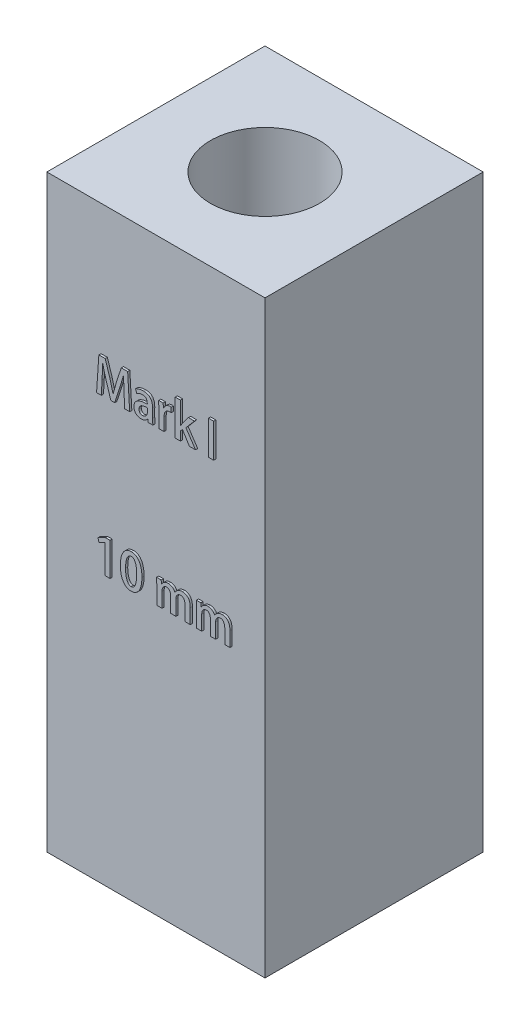
SolidWorks part; units mm, degrees
ref_plane "Alzado" through (0, 0, 0) normal (0, 0, 1) x (1, 0, 0)
ref_plane "Planta" through (0, 0, 0) normal (0, 1, 0) x (1, 0, 0)
ref_plane "Vista lateral" through (0, 0, 0) normal (1, 0, 0) x (0, 0, -1)
sketch "Croquis1" plane through (0, 0, 0) normal (0, 1, 0) x (1, 0, 0)
  line L1 (-5, 5) -> (5, 5)
  line L2 (-5, 5) -> (-5, -5)
  line L3 (-5, -5) -> (5, -5)
  line L4 (5, 5) -> (5, -5)
  line L5 (-5, 5) -> (5, -5) construction
  line L6 (-5, -5) -> (5, 5) construction
  circle A0 centre (0, 0) radius 2.5
  point P0 (0, 0)
  dimension "D1" = 5
  dimension "D2" = 10
extrude "Saliente-Extruir1" add sketch "Croquis1" along normal blind 27
sketch "Croquis2" plane through (0, 0, 5) normal (0, 0, 1) x (1, 0, 0)
  text T0 "Mark I\r\n \r\n10 mm" font "@Adobe Heiti Std R" height in points 5
split line "Línea de partición1"
extrude "Saliente-Extruir2" add sketch "Croquis2<2>" along normal blind 0.1
sketch "Croquis2<2>" plane through (0, 0, 5) normal (0, 0, 1) x (1, 0, 0) same geometry as "Croquis2"
